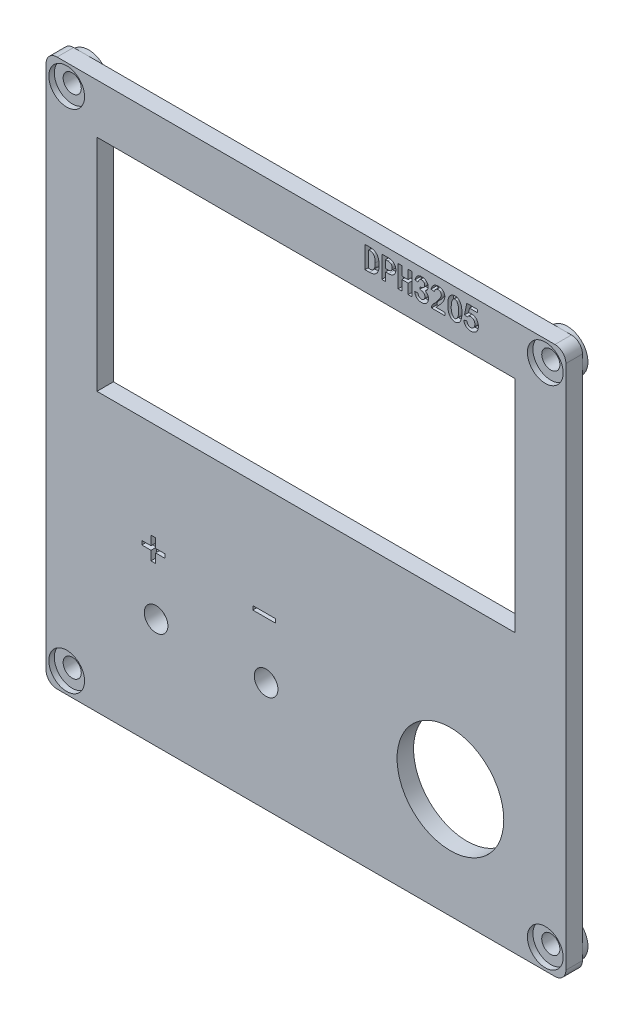
SolidWorks part; units mm, degrees
ref_plane "前视基准面" through (0, 0, 0) normal (0, 0, 1) x (1, 0, 0)
ref_plane "上视基准面" through (0, 0, 0) normal (0, 1, 0) x (1, 0, 0)
ref_plane "右视基准面" through (0, 0, 0) normal (1, 0, 0) x (0, 0, -1)
sketch "草图1" plane through (0, 0, 0) normal (0, 0, 1) x (1, 0, 0)
  line L0 (-27.25, -29.75) -> (-7.25, -29.75) construction
  line L1 (-45.25, -49.75) -> (45.25, -49.75)
  line L2 (-47.25, -47.75) -> (-47.25, 47.75)
  line L3 (-45.25, 49.75) -> (45.25, 49.75)
  line L4 (47.25, -47.75) -> (47.25, 47.75)
  line L5 (-47.25, -49.75) -> (47.25, 49.75) construction
  line L6 (-47.25, 49.75) -> (47.25, -49.75) construction
  line L7 (-38, 40.75) -> (38, 40.75)
  line L8 (-38, 40.75) -> (-38, 0.75)
  line L9 (-38, 0.75) -> (38, 0.75)
  line L10 (38, 40.75) -> (38, 0.75)
  arc A0 (-45.25, -49.75) -> (-47.25, -47.75) centre (-45.25, -47.75) cw
  arc A1 (45.25, -49.75) -> (47.25, -47.75) centre (45.25, -47.75) ccw
  arc A2 (45.25, 49.75) -> (47.25, 47.75) centre (45.25, 47.75) cw
  arc A3 (-47.25, 47.75) -> (-45.25, 49.75) centre (-45.25, 47.75) cw
  circle A4 centre (-27.25, -29.75) radius 2.15
  circle A5 centre (-7.25, -29.75) radius 2.15
  circle A6 centre (26.25, -29.75) radius 9.7
  point P0 (0, 0)
  point P22 (0, 40.75)
  point P23 (0, 49.75)
  dimension "D3" = 2
  dimension "D10" = 4.3
  dimension "D11" = 19.4
  dimension "D12" = 21
  dimension "D1" = 99.5
  dimension "D2" = 94.5
  dimension "D4" = 76
  dimension "D5" = 40
  dimension "D6" = 9
  dimension "D7" = 20
  dimension "D8" = 20
  dimension "D9" = 20
extrude "凸台-拉伸1" add sketch "草图1" along normal blind 3
sketch "草图2" plane through (0, 0, 3) normal (0, 0, 1) x (1, 0, 0)
  text T0 "DPH3205" font "黑体" height 4
  text T1 "+" font "黑体" height 6
  text T2 "-" font "黑体" height 6
extrude "切除-拉伸1" cut sketch "草图2" against normal blind 1
sketch "草图3" plane through (0, 0, 0) normal (0, 0, -1) x (-1, 0, 0)
  line L0 (-45.25, 49.75) -> (45.25, 49.75) construction
  line L1 (43.5, -46) -> (-43.5, -46) construction
  line L2 (43.5, -46) -> (43.5, 46) construction
  line L3 (43.5, 46) -> (-43.5, 46) construction
  line L4 (-43.5, -46) -> (-43.5, 46) construction
  line L5 (43.5, -46) -> (-43.5, 46) construction
  line L6 (43.5, 46) -> (-43.5, -46) construction
  circle A0 centre (-43.5, 46) radius 3.75
  circle A1 centre (43.5, 46) radius 3.75
  circle A2 centre (43.5, -46) radius 3.75
  circle A3 centre (-43.5, -46) radius 3.75
  point P0 (0, 0)
  dimension "D1" = 87
  dimension "D2" = 92
extrude "凸台-拉伸2" add sketch "草图3" along normal blind 1
sketch "草图4" plane through (0, 0, -1) normal (0, 0, -1) x (-1, 0, 0)
  circle A0 centre (-43.5, 46) radius 1.65
  circle A1 centre (43.5, 46) radius 1.65
  circle A2 centre (43.5, -46) radius 1.65
  circle A3 centre (-43.5, -46) radius 1.65
  dimension "D1" = 3.3
extrude "切除-拉伸2" cut sketch "草图4" against normal through all
sketch "草图5" plane through (0, 0, 3) normal (0, 0, 1) x (1, 0, 0)
  circle A0 centre (-43.5, 46) radius 3.25
  circle A1 centre (43.5, 46) radius 3.25
  circle A2 centre (43.5, -46) radius 3.25
  circle A3 centre (-43.5, -46) radius 3.25
  dimension "D1" = 6.5
extrude "切除-拉伸3" cut sketch "草图5" against normal blind 1
